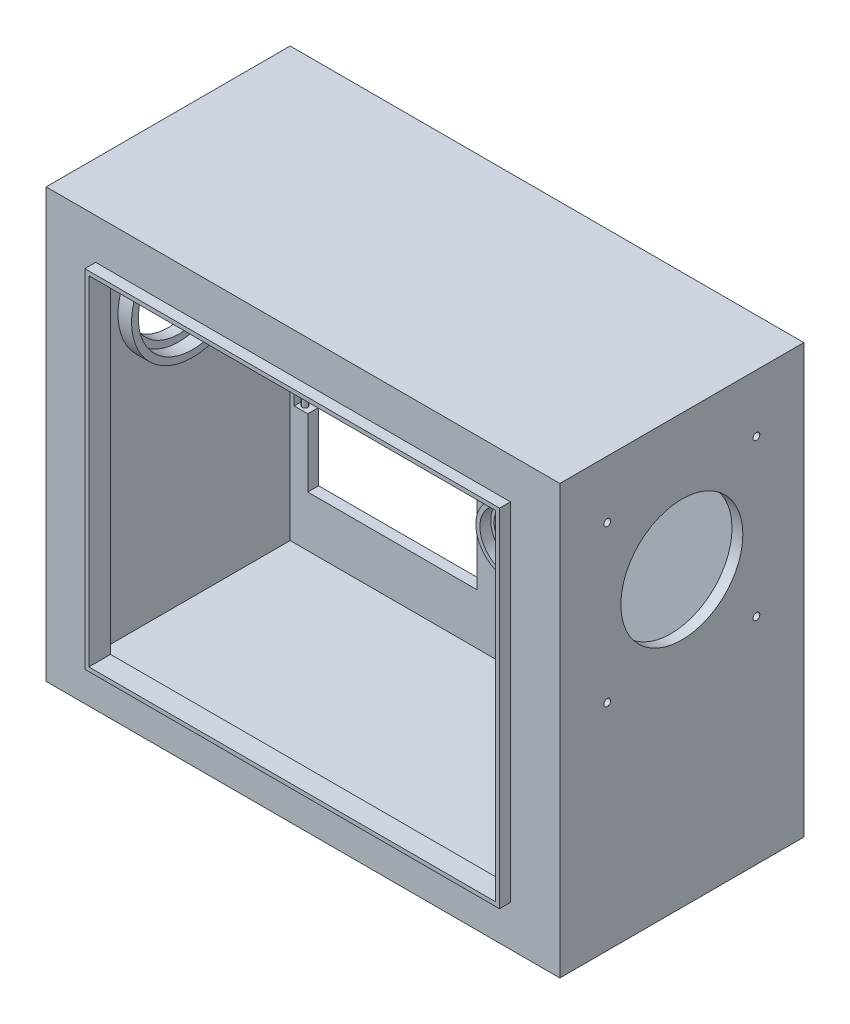
SolidWorks part; units mm, degrees
ref_plane "Alzado" through (0, 0, 0) normal (0, 0, 1) x (1, 0, 0)
ref_plane "Planta" through (0, 0, 0) normal (0, 1, 0) x (1, 0, 0)
ref_plane "Vista lateral" through (0, 0, 0) normal (1, 0, 0) x (0, 0, -1)
sketch "Croquis1" plane through (0, 0, 0) normal (0, 0, 1) x (1, 0, 0)
  line L0 (-189.5, 158) -> (189.5, 158)
  line L1 (-181.5, -150) -> (181.5, -150) construction
  line L2 (-181.5, -150) -> (-181.5, 150) construction
  line L3 (-181.5, 150) -> (181.5, 150) construction
  line L4 (181.5, -150) -> (181.5, 150) construction
  line L5 (-181.5, -150) -> (181.5, 150) construction
  line L6 (-181.5, 150) -> (181.5, -150) construction
  line L7 (189.5, -158) -> (189.5, 158)
  line L8 (-189.5, -158) -> (189.5, -158)
  line L9 (-189.5, -158) -> (-189.5, 158)
  point P0 (0, 0)
  dimension "D1" = 363
  dimension "D2" = 300
  dimension "D3" = 8
extrude "Saliente-Extruir1" add sketch "Croquis1" along normal blind 180
shell "Vaciado1" thickness 8 removed face at (0, 0, 180)
sketch "Croquis2" plane through (-189.5, 0, 0) normal (-1, 0, 0) x (0, 0, 1)
  line L0 (0, 158) -> (90, 158) construction
  line L1 (180, 158) -> (0, 158) construction
  circle A0 centre (90, 58) radius 35
extrude "Cortar-Extruir4" cut sketch "Croquis2" against normal blind 20 contours A0
sketch "Croquis4" plane through (-181.5, 0, 0) normal (1, 0, 0) x (0, 0, -1)
  circle A1 centre (-90, 58) radius 40
  circle A2 centre (-90, 58) radius 45
extrude "Saliente-Extruir4" add sketch "Croquis4" along normal blind 10
sketch "Croquis6" plane through (189.5, 0, 0) normal (1, 0, 0) x (0, 0, -1)
  line L0 (-90, 158) -> (-90, 58) construction
  line L1 (-180, 158) -> (0, 158) construction
  circle A0 centre (-90, 58) radius 45
  dimension "D1" = 90
extrude "Cortar-Extruir6" cut sketch "Croquis6" against normal blind 10 contours A0
sketch "Croquis7" plane through (0, 0, 8) normal (0, 0, 1) x (1, 0, 0)
  circle A3 centre (-2.5, -53) radius 21
  circle A4 centre (-2.5, -53) radius 24
  dimension "D1" = 42
  dimension "D2" = 48
extrude "Saliente-Extruir9" add sketch "Croquis7" along normal blind 18
ref_plane "Plano6" through (0, 0, 180) normal (0, 0, 1) x (1, 0, 0)
sketch "Croquis11" plane through (0, 0, 180) normal (0, 0, 1) x (1, 0, 0)
  line L1 (181.5, 150) -> (-181.5, 150)
  line L2 (181.5, 150) -> (181.5, -150)
  line L3 (181.5, -150) -> (-181.5, -150)
  line L4 (-181.5, 150) -> (-181.5, -150)
  line L5 (181.5, 150) -> (-181.5, -150) construction
  line L6 (181.5, -150) -> (-181.5, 150) construction
  line L7 (-150, 125) -> (150, 125)
  line L8 (-150, 125) -> (-150, -125)
  line L9 (-150, -125) -> (150, -125)
  line L10 (150, 125) -> (150, -125)
  line L11 (-150, 125) -> (150, -125) construction
  line L12 (-150, -125) -> (150, 125) construction
  point P0 (0, 0)
  point P7 (0, 0)
  dimension "D1" = 300
  dimension "D2" = 250
extrude "Saliente-Extruir10" add sketch "Croquis11" against normal blind 8
sketch "Croquis12" plane through (0, 0, 180) normal (0, 0, 1) x (1, 0, 0)
  line L1 (150, -125) -> (-150, -125)
  line L2 (150, -125) -> (150, 125)
  line L3 (150, 125) -> (-150, 125)
  line L4 (-150, -125) -> (-150, 125)
  line L5 (150, -125) -> (-150, 125) construction
  line L6 (150, 125) -> (-150, -125) construction
  line L7 (153, -128) -> (-153, -128)
  line L8 (153, -128) -> (153, 128)
  line L9 (153, 128) -> (-153, 128)
  line L10 (-153, -128) -> (-153, 128)
  line L11 (153, -128) -> (-153, 128) construction
  line L12 (153, 128) -> (-153, -128) construction
  point P0 (0, 0)
  point P8 (0, 0)
  dimension "D1" = 3
  dimension "D2" = 3
extrude "Saliente-Extruir11" add sketch "Croquis12" along normal blind 8
sketch "Croquis20" plane through (0, 0, 8) normal (0, 0, 1) x (1, 0, 0)
  circle A0 centre (-2.5, -53) radius 18.5
  circle A1 centre (-2.5, -53) radius 21
  circle A2 centre (-2.5, -53) radius 21 construction
  dimension "D1" = 37
extrude "Saliente-Extruir19" add sketch "Croquis20" along normal blind 10
hole_wizard "Taladro roscado M63" positions "Croquis3D6" profile "Croquis26" tap size "M6" standard "DIN" end condition through all
sketch3d "Croquis3D6"
  line L2 (-189.5, 0.5, 145) -> (-189.5, 115.5, 145) construction
  line L3 (-189.5, 0.5, 145) -> (-189.5, 0.5, 35) construction
  line L4 (-189.5, 0.5, 35) -> (-189.5, 115.5, 35) construction
  line L5 (-189.5, 115.5, 145) -> (-189.5, 115.5, 35) construction
  line L6 (-189.5, 0.5, 145) -> (-189.5, 115.5, 35) construction
  line L7 (-189.5, 0.5, 35) -> (-189.5, 115.5, 145) construction
  circle A1 centre (-189.5, 58, 90) radius 35 construction
  point P0 (-189.5, 115.5, 35)
  point P2 (-189.5, 115.5, 145)
  point P4 (-189.5, 0.5, 145)
  point P6 (-189.5, 0.5, 35)
  point P265 (-189.5, 58, 90)
  point P268 (-224.5, 58, 90)
  dimension "D1" = 115
  dimension "D2" = 0
  dimension "D3" = 110
sketch "Croquis26" plane through (-189.5, 115.5, 35) normal (0, 1, 0) x (0, 0, 1)
  line L0 (0, 0) -> (0, 379)
  line L1 (0, 379) -> (2.5, 379)
  line L2 (2.5, 379) -> (2.5, 0)
  line L5 (2.5, 0) -> (0, 0)
  line L11 (0, -6.35) -> (0, 107.95) construction
  dimension "Diámetro de perforador para roscar hasta el siguiente" = 5
  dimension "Profundidad de perforador para roscar hasta el siguiente" = 379
cosmetic thread "Rosca de taladro1" parameters "D2"=6
cosmetic thread "Rosca de taladro2" parameters "D2"=6
cosmetic thread "Rosca de taladro3" parameters "D2"=6
cosmetic thread "Rosca de taladro4" parameters "D2"=6
sketch "Croquis27" plane through (0, 0, 0) normal (0, 0, -1) x (-1, 0, 0)
  circle A0 centre (2.5, -53) radius 11
  circle A1 centre (2.5, -53) radius 21 construction
  dimension "D1" = 22
sketch "Croquis28" plane through (0, 0, 0) normal (0, 0, -1) x (-1, 0, 0)
  line L0 (0, 0) -> (106, 0) construction
  line L5 (168.5, 112.5) -> (43.5, 112.5)
  line L6 (168.5, 112.5) -> (168.5, -112.5)
  line L11 (168.5, -112.5) -> (43.5, -112.5)
  line L12 (43.5, 112.5) -> (43.5, -112.5)
  line L13 (168.5, 112.5) -> (43.5, -112.5) construction
  line L14 (168.5, -112.5) -> (43.5, 112.5) construction
  point P0 (106, 0)
  dimension "D1" = 125
  dimension "D2" = 225
  dimension "D3" = 106
extrude "Cortar-Extruir7" cut sketch "Croquis28" against normal blind 8 contours L6 L5 L12 L11
sketch "Croquis29" plane through (0, 0, 0) normal (0, 0, -1) x (-1, 0, 0)
  line L1 (168.5, 112.5) -> (168.5, -112.5) construction
  line L2 (168.5, 62.5) -> (178.5, 62.5)
  line L3 (168.5, 62.5) -> (168.5, 42.5)
  line L4 (168.5, 42.5) -> (178.5, 42.5)
  line L5 (178.5, 62.5) -> (178.5, 42.5)
  line L6 (168.5, 62.5) -> (178.5, 42.5) construction
  line L7 (168.5, 42.5) -> (178.5, 62.5) construction
  line L8 (168.5, -42.5) -> (178.5, -42.5)
  line L9 (168.5, -42.5) -> (168.5, -62.5)
  line L10 (168.5, -62.5) -> (178.5, -62.5)
  line L11 (178.5, -42.5) -> (178.5, -62.5)
  line L12 (168.5, -42.5) -> (178.5, -62.5) construction
  line L13 (168.5, -62.5) -> (178.5, -42.5) construction
  point P0 (173.5, -52.5)
  point P2 (173.5, 52.5)
  dimension "D1" = 50
  dimension "D2" = 20
  dimension "D3" = 10
  dimension "D4" = 50
  dimension "D5" = 20
  dimension "D6" = 10
extrude "Cortar-Extruir9" cut sketch "Croquis29" against normal blind 8
sketch "Croquis30" plane through (0, 42.5, 0) normal (0, 1, 0) x (1, 0, 0)
  line L4 (-178.5, -8) -> (-178.5, 0) construction
  line L5 (-168.5, 0) -> (-178.5, 0) construction
  circle A1 centre (-174.5, -4) radius 2
  dimension "D1" = 4
  dimension "D2" = 4
  dimension "D3" = 4
extrude "Saliente-Extruir20" add sketch "Croquis30" along normal blind 9
sketch "Croquis31" plane through (0, -62.5, 0) normal (0, 1, 0) x (1, 0, 0)
  line L0 (-178.5, -8) -> (-178.5, 0) construction
  line L1 (-168.5, 0) -> (-178.5, 0) construction
  circle A0 centre (-174.5, -4) radius 2
  dimension "D3" = 4
  dimension "D1" = 4
  dimension "D2" = 4
extrude "Saliente-Extruir21" add sketch "Croquis31" along normal blind 9
